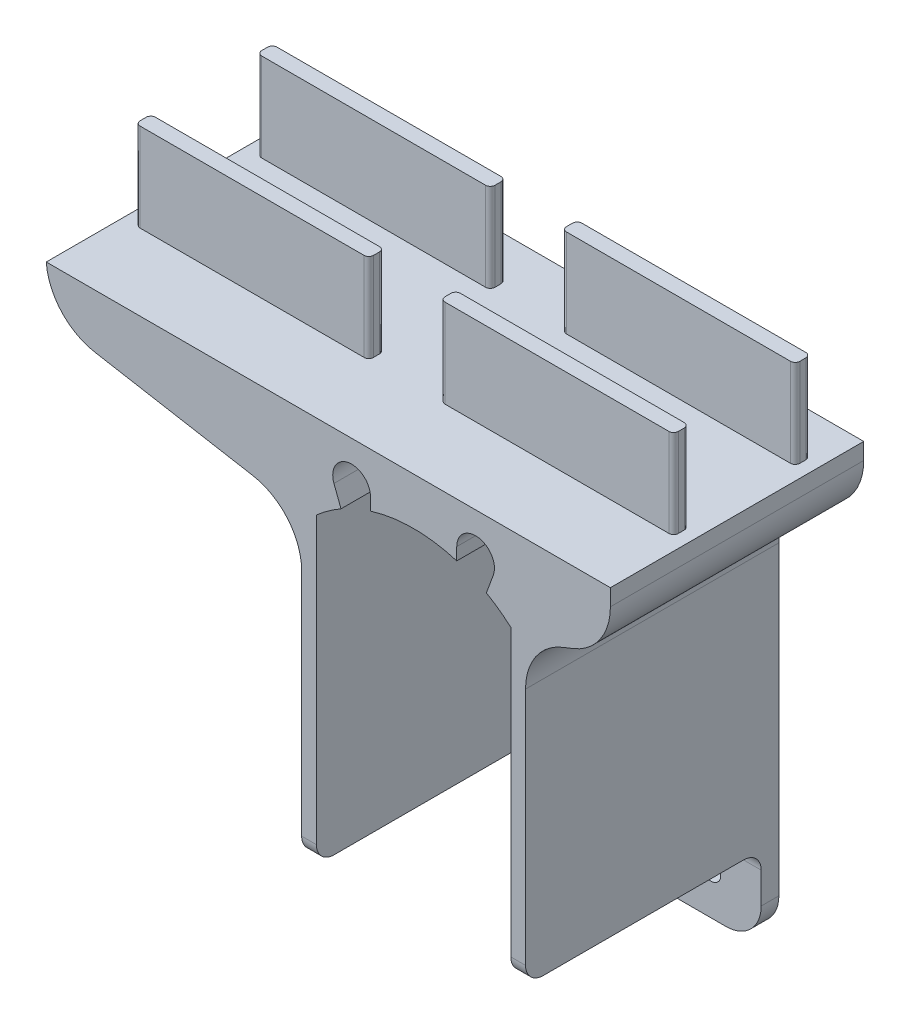
SolidWorks part; units mm, degrees
material "ABS"
ref_plane "Alzado" through (0, 0, 0) normal (0, 0, 1) x (1, 0, 0)
ref_plane "Planta" through (0, 0, 0) normal (0, 1, 0) x (1, 0, 0)
ref_plane "Vista lateral" through (0, 0, 0) normal (1, 0, 0) x (0, 0, -1)
sketch "Croquis4" plane through (0, 0, 0) normal (0, 0, 1) x (1, 0, 0)
  line L0 (-62.1753, -22.5138) -> (-62.1753, 45.4862)
  line L2 (-97.1753, -14.0138) -> (-97.1753, 36.9862) construction
  line L3 (-65.1753, 36.9862) -> (-65.1753, -14.0138) construction
  line L4 (-97.6753, -14.2397) -> (-97.6753, 37.2121)
  line L5 (-64.6753, 37.2121) -> (-64.6753, -14.2397)
  line L10 (-119.4893, 11.4862) -> (-39.0171, 11.4862) construction
  line L13 (-100.1753, -22.5138) -> (-100.1753, 45.4862)
  line L14 (-81.1753, 11.4862) -> (-81.1753, 55.3392) construction
  line L15 (-94.1753, 51.4862) -> (-68.1753, 51.4862)
  line L18 (-94.1753, -28.5138) -> (-68.1753, -28.5138)
  arc A0 (-62.1753, 45.4862) -> (-68.1753, 51.4862) centre (-68.1753, 45.4862) ccw
  arc A1 (-62.1753, -22.5138) -> (-68.1753, -28.5138) centre (-68.1753, -22.5138) cw
  arc A2 (-97.1753, -14.0138) -> (-65.1753, -14.0138) centre (-81.1753, 4.3195) ccw construction
  arc A3 (-65.1753, 36.9862) -> (-97.1753, 36.9862) centre (-81.1753, 18.6529) ccw construction
  arc A4 (-100.1753, -22.5138) -> (-94.1753, -28.5138) centre (-94.1753, -22.5138) ccw
  arc A8 (-68.6503, -23.214) -> (-72.6503, -23.214) centre (-70.6503, -21.5138) ccw construction
  arc A9 (-89.7003, -23.214) -> (-93.7003, -23.214) centre (-91.7003, -21.5138) ccw construction
  arc A10 (-93.7003, 46.1864) -> (-89.7003, 46.1864) centre (-91.7003, 44.4862) ccw construction
  arc A11 (-72.6503, 46.1864) -> (-68.6503, 46.1864) centre (-70.6503, 44.4862) ccw construction
  arc A12 (-64.6753, 37.2121) -> (-97.6753, 37.2121) centre (-81.1753, 18.6529) ccw
  arc A13 (-97.6753, -14.2397) -> (-64.6753, -14.2397) centre (-81.1753, 4.3195) ccw
  circle A14 centre (-91.7003, 44.4862) radius 1.6 construction
  circle A15 centre (-70.6503, 44.4862) radius 1.6 construction
  circle A16 centre (-91.7003, -21.5138) radius 1.6 construction
  circle A17 centre (-70.6503, -21.5138) radius 1.6 construction
  arc A20 (-100.1753, 45.4862) -> (-94.1753, 51.4862) centre (-94.1753, 45.4862) cw
  point P30 (-64.6753, 11.4862)
  point P39 (-81.1753, 51.4862)
  point P43 (-62.1753, 11.4862)
  point P48 (-100.1753, 11.4862)
  dimension "D2" = 3.2
  dimension "D3" = 6
  dimension "D4" = 2.5
  dimension "D5" = 40
  dimension "D1" = 0.5
extrude "Saliente-Extruir1" add sketch "Croquis4" along normal blind 3
sketch "Croquis5" plane through (0, 0, 3) normal (0, 0, 1) x (1, 0, 0)
  line L0 (-64.6753, -14.2397) -> (-64.6753, 37.2121) construction
  line L1 (-97.6753, 37.2121) -> (-97.6753, -14.2397) construction
  line L2 (-64.6753, -14.2397) -> (-64.6753, 37.2121)
  line L3 (-97.6753, 37.2121) -> (-97.6753, -14.2397)
  line L4 (-100.1753, 38.3026) -> (-100.1753, -14.2397)
  line L5 (-62.1753, -14.2397) -> (-62.1753, 38.3026)
  line L6 (-64.6753, -14.2397) -> (-62.1753, -14.2397)
  line L7 (-97.6753, -14.2397) -> (-100.1753, -14.2397)
  line L8 (-100.1753, 38.3026) -> (-100.1753, -15.3302) construction
  line L9 (-62.1753, -15.3302) -> (-62.1753, 38.3026) construction
  arc A1 (-64.6753, 37.2121) -> (-97.6753, 37.2121) centre (-81.1753, 18.6529) ccw construction
  arc A3 (-64.6753, 37.2121) -> (-97.6753, 37.2121) centre (-81.1753, 18.6529) ccw
  arc A4 (-62.1753, 38.3026) -> (-100.1753, 38.3026) centre (-81.1753, 18.6529) ccw
  arc A6 (-100.1753, -15.3302) -> (-62.1753, -15.3302) centre (-81.1753, 4.3195) ccw construction
  arc A7 (-97.6753, -14.2397) -> (-64.6753, -14.2397) centre (-81.1753, 4.3195) ccw construction
  dimension "D1" = 2.5
extrude "Saliente-Extruir2" add sketch "Croquis5" along normal blind 40
ref_plane "Plano1" through (0, 51.4862, 0) normal (0, -1, 0) x (-1, 0, 0)
sketch "Croquis6" plane through (0, 51.4862, 0) normal (0, -1, 0) x (-1, 0, 0)
  line L4 (49.7713, -7.6345) -> (49.7713, -8.6345)
  line L5 (88.7713, -6.6345) -> (50.7713, -6.6345)
  line L6 (89.7713, -8.6345) -> (89.7713, -7.6345)
  line L7 (50.7713, -9.6345) -> (88.7713, -9.6345)
  line L8 (49.7713, -7.6345) -> (49.7713, -8.6345) construction
  line L9 (88.7713, -6.6345) -> (50.7713, -6.6345) construction
  line L10 (89.7713, -8.6345) -> (89.7713, -7.6345) construction
  line L11 (50.7713, -9.6345) -> (88.7713, -9.6345) construction
  line L12 (49.7713, -28.2595) -> (49.7713, -29.2595)
  line L13 (88.7713, -27.2595) -> (50.7713, -27.2595)
  line L14 (89.7713, -29.2595) -> (89.7713, -28.2595)
  line L15 (50.7713, -30.2595) -> (88.7713, -30.2595)
  line L16 (49.7713, -28.2595) -> (49.7713, -29.2595) construction
  line L17 (88.7713, -27.2595) -> (50.7713, -27.2595) construction
  line L18 (89.7713, -29.2595) -> (89.7713, -28.2595) construction
  line L19 (50.7713, -30.2595) -> (88.7713, -30.2595) construction
  line L20 (141.5232, -29.2595) -> (141.5232, -28.2595)
  line L21 (102.5232, -30.2595) -> (140.5232, -30.2595)
  line L22 (101.5232, -28.2595) -> (101.5232, -29.2595)
  line L23 (140.5232, -27.2595) -> (102.5232, -27.2595)
  line L24 (141.5232, -29.2595) -> (141.5232, -28.2595) construction
  line L25 (102.5232, -30.2595) -> (140.5232, -30.2595) construction
  line L26 (101.5232, -28.2595) -> (101.5232, -29.2595) construction
  line L27 (140.5232, -27.2595) -> (102.5232, -27.2595) construction
  line L28 (141.5232, -8.6345) -> (141.5232, -7.6345)
  line L29 (102.5232, -9.6345) -> (140.5232, -9.6345)
  line L30 (101.5232, -7.6345) -> (101.5232, -8.6345)
  line L31 (140.5232, -6.6345) -> (102.5232, -6.6345)
  line L32 (141.5232, -8.6345) -> (141.5232, -7.6345) construction
  line L33 (102.5232, -9.6345) -> (140.5232, -9.6345) construction
  line L34 (101.5232, -7.6345) -> (101.5232, -8.6345) construction
  line L35 (140.5232, -6.6345) -> (102.5232, -6.6345) construction
  arc A4 (50.7713, -6.6345) -> (49.7713, -7.6345) centre (50.7713, -7.6345) ccw
  arc A5 (89.7713, -7.6345) -> (88.7713, -6.6345) centre (88.7713, -7.6345) ccw
  arc A6 (88.7713, -9.6345) -> (89.7713, -8.6345) centre (88.7713, -8.6345) ccw
  arc A7 (49.7713, -8.6345) -> (50.7713, -9.6345) centre (50.7713, -8.6345) ccw
  arc A8 (50.7713, -6.6345) -> (49.7713, -7.6345) centre (50.7713, -7.6345) ccw construction
  arc A9 (89.7713, -7.6345) -> (88.7713, -6.6345) centre (88.7713, -7.6345) ccw construction
  arc A10 (88.7713, -9.6345) -> (89.7713, -8.6345) centre (88.7713, -8.6345) ccw construction
  arc A11 (49.7713, -8.6345) -> (50.7713, -9.6345) centre (50.7713, -8.6345) ccw construction
  arc A12 (50.7713, -27.2595) -> (49.7713, -28.2595) centre (50.7713, -28.2595) ccw
  arc A13 (89.7713, -28.2595) -> (88.7713, -27.2595) centre (88.7713, -28.2595) ccw
  arc A14 (88.7713, -30.2595) -> (89.7713, -29.2595) centre (88.7713, -29.2595) ccw
  arc A15 (49.7713, -29.2595) -> (50.7713, -30.2595) centre (50.7713, -29.2595) ccw
  arc A16 (50.7713, -27.2595) -> (49.7713, -28.2595) centre (50.7713, -28.2595) ccw construction
  arc A17 (89.7713, -28.2595) -> (88.7713, -27.2595) centre (88.7713, -28.2595) ccw construction
  arc A18 (88.7713, -30.2595) -> (89.7713, -29.2595) centre (88.7713, -29.2595) ccw construction
  arc A19 (49.7713, -29.2595) -> (50.7713, -30.2595) centre (50.7713, -29.2595) ccw construction
  arc A20 (140.5232, -30.2595) -> (141.5232, -29.2595) centre (140.5232, -29.2595) ccw
  arc A21 (101.5232, -29.2595) -> (102.5232, -30.2595) centre (102.5232, -29.2595) ccw
  arc A22 (102.5232, -27.2595) -> (101.5232, -28.2595) centre (102.5232, -28.2595) ccw
  arc A23 (141.5232, -28.2595) -> (140.5232, -27.2595) centre (140.5232, -28.2595) ccw
  arc A24 (140.5232, -30.2595) -> (141.5232, -29.2595) centre (140.5232, -29.2595) ccw construction
  arc A25 (101.5232, -29.2595) -> (102.5232, -30.2595) centre (102.5232, -29.2595) ccw construction
  arc A26 (102.5232, -27.2595) -> (101.5232, -28.2595) centre (102.5232, -28.2595) ccw construction
  arc A27 (141.5232, -28.2595) -> (140.5232, -27.2595) centre (140.5232, -28.2595) ccw construction
  arc A28 (140.5232, -9.6345) -> (141.5232, -8.6345) centre (140.5232, -8.6345) ccw
  arc A29 (101.5232, -8.6345) -> (102.5232, -9.6345) centre (102.5232, -8.6345) ccw
  arc A30 (102.5232, -6.6345) -> (101.5232, -7.6345) centre (102.5232, -7.6345) ccw
  arc A31 (141.5232, -7.6345) -> (140.5232, -6.6345) centre (140.5232, -7.6345) ccw
  arc A32 (140.5232, -9.6345) -> (141.5232, -8.6345) centre (140.5232, -8.6345) ccw construction
  arc A33 (101.5232, -8.6345) -> (102.5232, -9.6345) centre (102.5232, -8.6345) ccw construction
  arc A34 (102.5232, -6.6345) -> (101.5232, -7.6345) centre (102.5232, -7.6345) ccw construction
  arc A35 (141.5232, -7.6345) -> (140.5232, -6.6345) centre (140.5232, -7.6345) ccw construction
  dimension "D1" = 0
  dimension "D2" = 0
  dimension "D3" = 0
  dimension "D4" = 0
ref_plane "Plano2" through (0, 0, 30.2595) normal (0, 0, 1) x (1, 0, 0)
sketch "Croquis7" plane through (0, 0, 30.2595) normal (0, 0, 1) x (1, 0, 0)
  line L0 (-141.5232, 51.4862) -> (-140.5232, 51.4862) construction
  line L1 (-50.7713, 51.4862) -> (-49.7713, 51.4862) construction
  line L2 (-141.5232, 51.4862) -> (-140.5232, 51.4862) construction
  line L3 (-50.7713, 51.4862) -> (-49.7713, 51.4862) construction
  line L4 (-143.5232, 51.4862) -> (-143.5232, 43.8023)
  line L5 (-62.1753, 45.4862) -> (-62.1753, 38.3026) construction
  line L6 (-100.1753, 38.3026) -> (-100.1753, 45.4862) construction
  line L7 (-62.1753, 45.4862) -> (-62.1753, 38.3026) construction
  line L8 (-100.1753, 38.3026) -> (-100.1753, 45.4862) construction
  line L9 (-143.5232, 43.8023) -> (-100.1753, 36.1589)
  line L10 (-47.7713, 51.4862) -> (-47.7713, 41.8929)
  line L11 (-47.7713, 41.8929) -> (-62.1753, 36.1589)
  line L13 (-143.5232, 51.4862) -> (-47.7713, 51.4862)
  line L14 (-100.1753, 36.1589) -> (-100.1753, 38.3026)
  line L15 (-62.1753, 36.1589) -> (-62.1753, 38.3026)
  arc A0 (-62.1753, 38.3026) -> (-100.1753, 38.3026) centre (-81.1753, 18.6529) ccw construction
  arc A1 (-62.1753, 38.3026) -> (-100.1753, 38.3026) centre (-81.1753, 18.6529) ccw
  dimension "D1" = 2
  dimension "D2" = 2
  dimension "D3" = 100
extrude "Saliente-Extruir3" add sketch "Croquis7" against normal up to surface (30.2595 mm away) from surface up to face at (-81.1753, 11.4862, 0) starting at face at (-81.1753, 13.5035, 43)
fillet "Redondeo1" radius 10 4 edges at (-62.1753, 36.1589, 21.5) (-47.7713, 41.8929, 21.5) (-143.5232, 43.8023, 21.5) (-100.1753, 36.1589, 21.5)
sketch "Croquis8" plane through (0, 51.4862, 0) normal (0, 1, 0) x (1, 0, 0)
  line L0 (-88.7713, -6.6345) -> (-50.7713, -6.6345) construction
  line L1 (-49.7713, -7.6345) -> (-49.7713, -8.6345) construction
  line L2 (-50.7713, -9.6345) -> (-88.7713, -9.6345) construction
  line L3 (-89.7713, -8.6345) -> (-89.7713, -7.6345) construction
  line L4 (-88.7713, -27.2595) -> (-50.7713, -27.2595) construction
  line L5 (-49.7713, -28.2595) -> (-49.7713, -29.2595) construction
  line L6 (-50.7713, -30.2595) -> (-88.7713, -30.2595) construction
  line L7 (-89.7713, -29.2595) -> (-89.7713, -28.2595) construction
  line L8 (-140.5232, -27.2595) -> (-102.5232, -27.2595) construction
  line L9 (-101.5232, -28.2595) -> (-101.5232, -29.2595) construction
  line L10 (-102.5232, -30.2595) -> (-140.5232, -30.2595) construction
  line L11 (-141.5232, -29.2595) -> (-141.5232, -28.2595) construction
  line L12 (-140.5232, -6.6345) -> (-102.5232, -6.6345) construction
  line L13 (-101.5232, -7.6345) -> (-101.5232, -8.6345) construction
  line L14 (-102.5232, -9.6345) -> (-140.5232, -9.6345) construction
  line L15 (-141.5232, -8.6345) -> (-141.5232, -7.6345) construction
  line L16 (-88.7713, -6.6345) -> (-50.7713, -6.6345) construction
  line L17 (-49.7713, -7.6345) -> (-49.7713, -8.6345) construction
  line L18 (-50.7713, -9.6345) -> (-88.7713, -9.6345) construction
  line L19 (-89.7713, -8.6345) -> (-89.7713, -7.6345) construction
  line L20 (-88.7713, -27.2595) -> (-50.7713, -27.2595) construction
  line L21 (-49.7713, -28.2595) -> (-49.7713, -29.2595) construction
  line L22 (-50.7713, -30.2595) -> (-88.7713, -30.2595) construction
  line L23 (-89.7713, -29.2595) -> (-89.7713, -28.2595) construction
  line L24 (-140.5232, -27.2595) -> (-102.5232, -27.2595) construction
  line L25 (-101.5232, -28.2595) -> (-101.5232, -29.2595) construction
  line L26 (-102.5232, -30.2595) -> (-140.5232, -30.2595) construction
  line L27 (-141.5232, -29.2595) -> (-141.5232, -28.2595) construction
  line L28 (-140.5232, -6.6345) -> (-102.5232, -6.6345) construction
  line L29 (-101.5232, -7.6345) -> (-101.5232, -8.6345) construction
  line L30 (-102.5232, -9.6345) -> (-140.5232, -9.6345) construction
  line L31 (-141.5232, -8.6345) -> (-141.5232, -7.6345) construction
  line L36 (-88.7713, -6.8345) -> (-50.7713, -6.8345)
  line L37 (-49.9713, -7.6345) -> (-49.9713, -8.6345)
  line L38 (-50.7713, -9.4345) -> (-88.7713, -9.4345)
  line L39 (-89.5713, -8.6345) -> (-89.5713, -7.6345)
  line L40 (-88.7713, -27.4595) -> (-50.7713, -27.4595)
  line L41 (-49.9713, -28.2595) -> (-49.9713, -29.2595)
  line L42 (-50.7713, -30.0595) -> (-88.7713, -30.0595)
  line L43 (-89.5713, -29.2595) -> (-89.5713, -28.2595)
  line L44 (-140.5232, -27.4595) -> (-102.5232, -27.4595)
  line L45 (-101.7232, -28.2595) -> (-101.7232, -29.2595)
  line L46 (-102.5232, -30.0595) -> (-140.5232, -30.0595)
  line L47 (-141.3232, -29.2595) -> (-141.3232, -28.2595)
  line L48 (-140.5232, -6.8345) -> (-102.5232, -6.8345)
  line L49 (-101.7232, -7.6345) -> (-101.7232, -8.6345)
  line L50 (-102.5232, -9.4345) -> (-140.5232, -9.4345)
  line L51 (-141.3232, -8.6345) -> (-141.3232, -7.6345)
  arc A0 (-49.7713, -7.6345) -> (-50.7713, -6.6345) centre (-50.7713, -7.6345) ccw construction
  arc A1 (-50.7713, -9.6345) -> (-49.7713, -8.6345) centre (-50.7713, -8.6345) ccw construction
  arc A2 (-89.7713, -8.6345) -> (-88.7713, -9.6345) centre (-88.7713, -8.6345) ccw construction
  arc A3 (-88.7713, -6.6345) -> (-89.7713, -7.6345) centre (-88.7713, -7.6345) ccw construction
  arc A4 (-49.7713, -28.2595) -> (-50.7713, -27.2595) centre (-50.7713, -28.2595) ccw construction
  arc A5 (-50.7713, -30.2595) -> (-49.7713, -29.2595) centre (-50.7713, -29.2595) ccw construction
  arc A6 (-89.7713, -29.2595) -> (-88.7713, -30.2595) centre (-88.7713, -29.2595) ccw construction
  arc A7 (-88.7713, -27.2595) -> (-89.7713, -28.2595) centre (-88.7713, -28.2595) ccw construction
  arc A8 (-101.5232, -28.2595) -> (-102.5232, -27.2595) centre (-102.5232, -28.2595) ccw construction
  arc A9 (-102.5232, -30.2595) -> (-101.5232, -29.2595) centre (-102.5232, -29.2595) ccw construction
  arc A10 (-141.5232, -29.2595) -> (-140.5232, -30.2595) centre (-140.5232, -29.2595) ccw construction
  arc A11 (-140.5232, -27.2595) -> (-141.5232, -28.2595) centre (-140.5232, -28.2595) ccw construction
  arc A12 (-101.5232, -7.6345) -> (-102.5232, -6.6345) centre (-102.5232, -7.6345) ccw construction
  arc A13 (-102.5232, -9.6345) -> (-101.5232, -8.6345) centre (-102.5232, -8.6345) ccw construction
  arc A14 (-141.5232, -8.6345) -> (-140.5232, -9.6345) centre (-140.5232, -8.6345) ccw construction
  arc A15 (-140.5232, -6.6345) -> (-141.5232, -7.6345) centre (-140.5232, -7.6345) ccw construction
  arc A16 (-49.7713, -7.6345) -> (-50.7713, -6.6345) centre (-50.7713, -7.6345) ccw construction
  arc A17 (-50.7713, -9.6345) -> (-49.7713, -8.6345) centre (-50.7713, -8.6345) ccw construction
  arc A18 (-89.7713, -8.6345) -> (-88.7713, -9.6345) centre (-88.7713, -8.6345) ccw construction
  arc A19 (-88.7713, -6.6345) -> (-89.7713, -7.6345) centre (-88.7713, -7.6345) ccw construction
  arc A20 (-49.7713, -28.2595) -> (-50.7713, -27.2595) centre (-50.7713, -28.2595) ccw construction
  arc A21 (-50.7713, -30.2595) -> (-49.7713, -29.2595) centre (-50.7713, -29.2595) ccw construction
  arc A22 (-89.7713, -29.2595) -> (-88.7713, -30.2595) centre (-88.7713, -29.2595) ccw construction
  arc A23 (-88.7713, -27.2595) -> (-89.7713, -28.2595) centre (-88.7713, -28.2595) ccw construction
  arc A24 (-101.5232, -28.2595) -> (-102.5232, -27.2595) centre (-102.5232, -28.2595) ccw construction
  arc A25 (-102.5232, -30.2595) -> (-101.5232, -29.2595) centre (-102.5232, -29.2595) ccw construction
  arc A26 (-141.5232, -29.2595) -> (-140.5232, -30.2595) centre (-140.5232, -29.2595) ccw construction
  arc A27 (-140.5232, -27.2595) -> (-141.5232, -28.2595) centre (-140.5232, -28.2595) ccw construction
  arc A28 (-101.5232, -7.6345) -> (-102.5232, -6.6345) centre (-102.5232, -7.6345) ccw construction
  arc A29 (-102.5232, -9.6345) -> (-101.5232, -8.6345) centre (-102.5232, -8.6345) ccw construction
  arc A30 (-141.5232, -8.6345) -> (-140.5232, -9.6345) centre (-140.5232, -8.6345) ccw construction
  arc A31 (-140.5232, -6.6345) -> (-141.5232, -7.6345) centre (-140.5232, -7.6345) ccw construction
  arc A36 (-49.9713, -7.6345) -> (-50.7713, -6.8345) centre (-50.7713, -7.6345) ccw
  arc A37 (-50.7713, -9.4345) -> (-49.9713, -8.6345) centre (-50.7713, -8.6345) ccw
  arc A38 (-89.5713, -8.6345) -> (-88.7713, -9.4345) centre (-88.7713, -8.6345) ccw
  arc A39 (-88.7713, -6.8345) -> (-89.5713, -7.6345) centre (-88.7713, -7.6345) ccw
  arc A40 (-49.9713, -28.2595) -> (-50.7713, -27.4595) centre (-50.7713, -28.2595) ccw
  arc A41 (-50.7713, -30.0595) -> (-49.9713, -29.2595) centre (-50.7713, -29.2595) ccw
  arc A42 (-89.5713, -29.2595) -> (-88.7713, -30.0595) centre (-88.7713, -29.2595) ccw
  arc A43 (-88.7713, -27.4595) -> (-89.5713, -28.2595) centre (-88.7713, -28.2595) ccw
  arc A44 (-101.7232, -28.2595) -> (-102.5232, -27.4595) centre (-102.5232, -28.2595) ccw
  arc A45 (-102.5232, -30.0595) -> (-101.7232, -29.2595) centre (-102.5232, -29.2595) ccw
  arc A46 (-141.3232, -29.2595) -> (-140.5232, -30.0595) centre (-140.5232, -29.2595) ccw
  arc A47 (-140.5232, -27.4595) -> (-141.3232, -28.2595) centre (-140.5232, -28.2595) ccw
  arc A48 (-101.7232, -7.6345) -> (-102.5232, -6.8345) centre (-102.5232, -7.6345) ccw
  arc A49 (-102.5232, -9.4345) -> (-101.7232, -8.6345) centre (-102.5232, -8.6345) ccw
  arc A50 (-141.3232, -8.6345) -> (-140.5232, -9.4345) centre (-140.5232, -8.6345) ccw
  arc A51 (-140.5232, -6.8345) -> (-141.3232, -7.6345) centre (-140.5232, -7.6345) ccw
  dimension "D1" = 0.2
extrude "Saliente-Extruir4" add sketch "Croquis8" along normal blind 15
sketch "Croquis9" plane through (0, 0, 0) normal (0, 0, -1) x (-1, 0, 0)
  circle A0 centre (91.7003, -21.5138) radius 1.6 construction
  circle A1 centre (70.6503, -21.5138) radius 1.6 construction
  circle A4 centre (91.7003, -21.5138) radius 1.6
  circle A5 centre (70.6503, -21.5138) radius 1.6
sketch "Croquis12" plane through (0, 0, 0) normal (0, 0, -1) x (-1, 0, 0)
  circle A0 centre (91.7003, -21.5138) radius 1.6 construction
  circle A1 centre (70.6503, -21.5138) radius 1.6 construction
  circle A2 centre (91.7003, -21.5138) radius 1.6
  circle A3 centre (70.6503, -21.5138) radius 1.6
  circle A4 centre (91.7003, 44.4862) radius 1.6 construction
  circle A5 centre (70.6503, 44.4862) radius 1.6 construction
  circle A6 centre (91.7003, 44.4862) radius 1.6
  circle A7 centre (70.6503, 44.4862) radius 1.6
extrude "Cortar-Extruir2" cut sketch "Croquis12" against normal blind 3
sketch "Croquis13" plane through (0, 0, 0) normal (0, 0, -1) x (-1, 0, 0)
  circle A0 centre (91.7003, 44.4862) radius 1.6 construction
  circle A1 centre (70.6503, 44.4862) radius 1.6 construction
  circle A2 centre (91.7003, 44.4862) radius 1.6 construction
  circle A3 centre (70.6503, 44.4862) radius 1.6 construction
  circle A4 centre (70.6503, 44.4862) radius 3.2
  circle A5 centre (91.7003, 44.4862) radius 3.2
  dimension "D1" = 6.4
extrude "Cortar-Extruir3" cut sketch "Croquis13" against normal through all from offset 3 offset against normal yes
fillet "Redondeo2" radius 3 4 edges at (-98.9253, -14.2397, 43) (-63.4253, -14.2397, 43) (-98.9253, -14.2397, 3) (-63.4253, -14.2397, 3)
sketch "Croquis14" plane through (0, 0, 43) normal (0, 0, 1) x (1, 0, 0)
  line L0 (-94.6911, 43.3481) -> (-92.3546, 37.2081)
  line L1 (-92.3546, 37.2081) -> (-88.5003, 37.2081)
  line L2 (-88.5003, 37.2081) -> (-88.5003, 44.4862)
  line L3 (-73.8503, 44.4862) -> (-73.8503, 37.2081)
  line L5 (-69.9105, 37.2081) -> (-67.6459, 43.3846)
  line L6 (-73.8503, 37.2081) -> (-69.9105, 37.2081)
  circle A0 centre (-70.6503, 44.4862) radius 3.2 construction
  circle A1 centre (-91.7003, 44.4862) radius 3.2 construction
  arc A2 (-67.6459, 43.3846) -> (-73.8503, 44.4862) centre (-70.6503, 44.4862) ccw
  arc A3 (-88.5003, 44.4862) -> (-94.6911, 43.3481) centre (-91.7003, 44.4862) ccw
  arc A4 (-91.3521, 41.3052) -> (-97.6753, 37.2121) centre (-81.1753, 18.6529) ccw construction
  arc A5 (-91.3521, 41.3052) -> (-97.6753, 37.2121) centre (-81.1753, 18.6529) ccw construction
extrude "Cortar-Extruir4" cut sketch "Croquis14" against normal up to surface (40 mm away) up to face at (-72.2503, 44.4862, 3)
